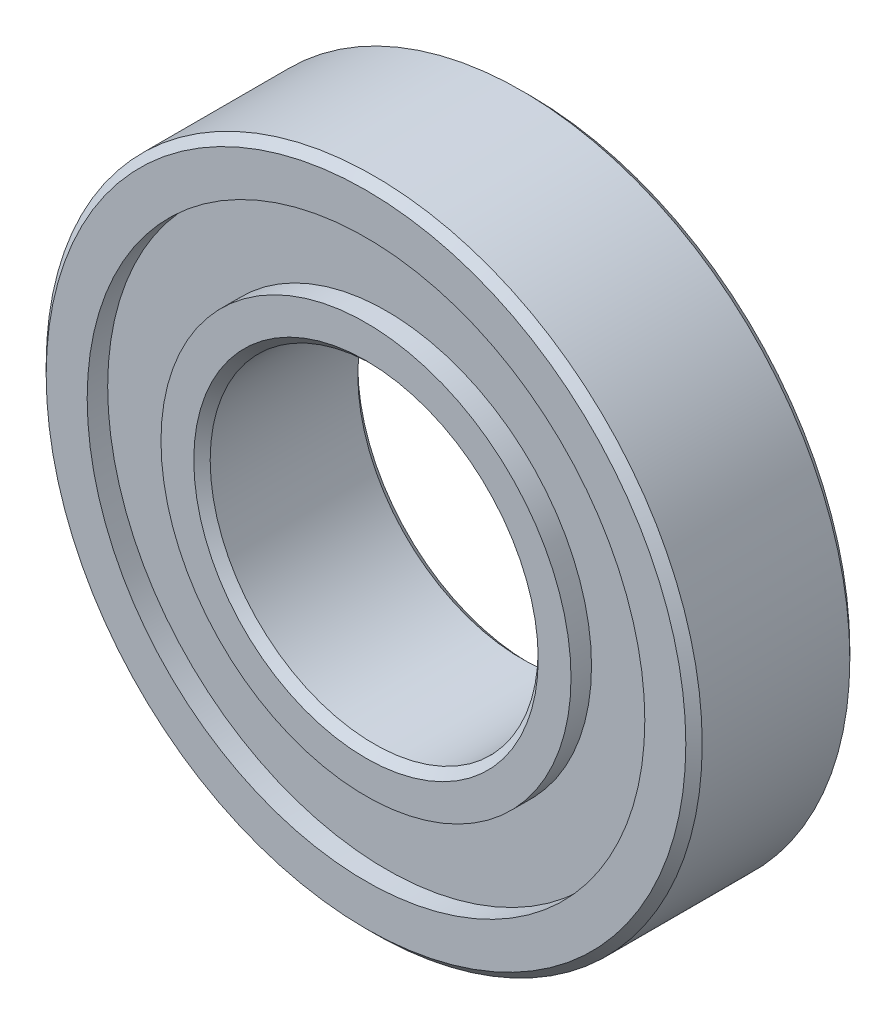
SolidWorks part; units mm, degrees
ref_plane "Ebene vorne" through (0, 0, 0) normal (0, 0, 1) x (1, 0, 0)
ref_plane "Ebene oben" through (0, 0, 0) normal (0, 1, 0) x (1, 0, 0)
ref_plane "Ebene rechts" through (0, 0, 0) normal (1, 0, 0) x (0, 0, -1)
sketch "Skizze2" plane through (0, 0, 0) normal (1, 0, 0) x (0, 0, -1)
  line L0 (-11.8458, 0) -> (13.4965, 0) construction
  line L1 (0, 16.288) -> (0, -14.1034) construction
  line L2 (-1, 2) -> (1, 2)
  line L3 (1, 2) -> (1, 2.5)
  line L4 (1, 2.5) -> (0.75, 2.5)
  line L5 (0.75, 2.5) -> (0.75, 3.4)
  line L6 (0.75, 3.4) -> (1, 3.4)
  line L7 (1, 3.4) -> (1, 4)
  line L8 (1, 4) -> (-1, 4)
  line L9 (-1, 3.4) -> (-1, 4)
  line L10 (-0.75, 3.4) -> (-1, 3.4)
  line L11 (-0.75, 2.5) -> (-0.75, 3.4)
  line L12 (-1, 2.5) -> (-0.75, 2.5)
  line L13 (-1, 2) -> (-1, 2.5)
  point P5 (0, 4)
  point P19 (0, 2)
  dimension "D1" = 4
  dimension "D2" = 8
  dimension "D3" = 2
  dimension "D4" = 5
  dimension "D5" = 6.8
  dimension "D6" = 1.5
revolve "Rotation1" add sketch "Skizze2" angle 360 about L0
ref_axis "Achse1" through (0, 0, -1.1) along (0, 0, 1)
chamfer "Fase1" distance 0.1 angle 45 4 edges at (2, 0, -1) (2, 0, 1) (4, 0, -1) (4, 0, 1)
